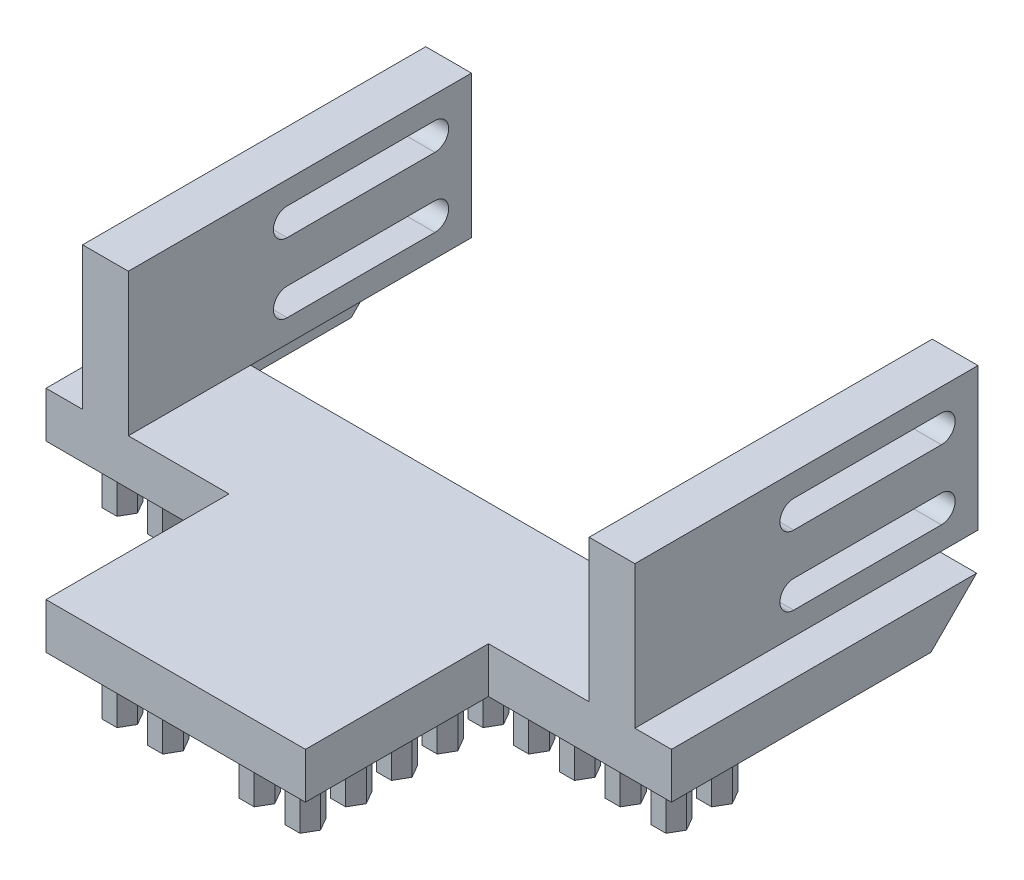
SolidWorks part; units mm, degrees
ref_plane "Front Plane" through (0, 0, 0) normal (0, 0, 1) x (1, 0, 0)
ref_plane "Top Plane" through (0, 0, 0) normal (0, 1, 0) x (1, 0, 0)
ref_plane "Right Plane" through (0, 0, 0) normal (1, 0, 0) x (0, 0, -1)
sketch "Sketch2" plane through (0, 0, 0) normal (0, 1, 0) x (1, 0, 0)
  line L0 (60, 0) -> (-60, 0) construction
  line L1 (-53.2909, -10) -> (-51.6454, -12.85)
  line L2 (-63.2909, 0) -> (-61.6454, -2.85)
  line L3 (-61.6454, -2.85) -> (-58.3546, -2.85)
  line L4 (-58.3546, -2.85) -> (-56.7091, 0)
  line L5 (-56.7091, 0) -> (-58.3546, 2.85)
  line L6 (-58.3546, 2.85) -> (-61.6454, 2.85)
  line L7 (-61.6454, 2.85) -> (-63.2909, 0)
  line L15 (-60, 0) -> (-60, -10) construction
  line L30 (-63.2909, -10) -> (-61.6454, -12.85)
  line L31 (-61.6454, -12.85) -> (-58.3546, -12.85)
  line L32 (-58.3546, -12.85) -> (-56.7091, -10)
  line L33 (-56.7091, -10) -> (-58.3546, -7.15)
  line L34 (-58.3546, -7.15) -> (-61.6454, -7.15)
  line L35 (-61.6454, -7.15) -> (-63.2909, -10)
  line L36 (-51.6454, -12.85) -> (-48.3546, -12.85)
  line L37 (-48.3546, -12.85) -> (-46.7091, -10)
  line L38 (-46.7091, -10) -> (-48.3546, -7.15)
  line L39 (-48.3546, -7.15) -> (-51.6454, -7.15)
  line L40 (-51.6454, -7.15) -> (-53.2909, -10)
  line L41 (-53.2909, 0) -> (-51.6454, -2.85)
  line L42 (-51.6454, -2.85) -> (-48.3546, -2.85)
  line L43 (-48.3546, -2.85) -> (-46.7091, 0)
  line L44 (-46.7091, 0) -> (-48.3546, 2.85)
  line L45 (-48.3546, 2.85) -> (-51.6454, 2.85)
  line L46 (-51.6454, 2.85) -> (-53.2909, 0)
  line L47 (-43.2909, -10) -> (-41.6454, -12.85)
  line L48 (-41.6454, -12.85) -> (-38.3546, -12.85)
  line L49 (-38.3546, -12.85) -> (-36.7091, -10)
  line L50 (-36.7091, -10) -> (-38.3546, -7.15)
  line L51 (-38.3546, -7.15) -> (-41.6454, -7.15)
  line L52 (-41.6454, -7.15) -> (-43.2909, -10)
  line L53 (-43.2909, 0) -> (-41.6454, -2.85)
  line L54 (-41.6454, -2.85) -> (-38.3546, -2.85)
  line L55 (-38.3546, -2.85) -> (-36.7091, 0)
  line L56 (-36.7091, 0) -> (-38.3546, 2.85)
  line L57 (-38.3546, 2.85) -> (-41.6454, 2.85)
  line L58 (-41.6454, 2.85) -> (-43.2909, 0)
  line L59 (-33.2909, -10) -> (-31.6454, -12.85)
  line L60 (-31.6454, -12.85) -> (-28.3546, -12.85)
  line L61 (-28.3546, -12.85) -> (-26.7091, -10)
  line L62 (-26.7091, -10) -> (-28.3546, -7.15)
  line L63 (-28.3546, -7.15) -> (-31.6454, -7.15)
  line L64 (-31.6454, -7.15) -> (-33.2909, -10)
  line L65 (-33.2909, 0) -> (-31.6454, -2.85)
  line L66 (-31.6454, -2.85) -> (-28.3546, -2.85)
  line L67 (-28.3546, -2.85) -> (-26.7091, 0)
  line L68 (-26.7091, 0) -> (-28.3546, 2.85)
  line L69 (-28.3546, 2.85) -> (-31.6454, 2.85)
  line L70 (-31.6454, 2.85) -> (-33.2909, 0)
  line L71 (-23.2909, -10) -> (-21.6454, -12.85)
  line L72 (-21.6454, -12.85) -> (-18.3546, -12.85)
  line L73 (-18.3546, -12.85) -> (-16.7091, -10)
  line L74 (-16.7091, -10) -> (-18.3546, -7.15)
  line L75 (-18.3546, -7.15) -> (-21.6454, -7.15)
  line L76 (-21.6454, -7.15) -> (-23.2909, -10)
  line L77 (-23.2909, 0) -> (-21.6454, -2.85)
  line L78 (-21.6454, -2.85) -> (-18.3546, -2.85)
  line L79 (-18.3546, -2.85) -> (-16.7091, 0)
  line L80 (-16.7091, 0) -> (-18.3546, 2.85)
  line L81 (-18.3546, 2.85) -> (-21.6454, 2.85)
  line L82 (-21.6454, 2.85) -> (-23.2909, 0)
  line L83 (-13.2909, -10) -> (-11.6454, -12.85)
  line L84 (-11.6454, -12.85) -> (-8.3546, -12.85)
  line L85 (-8.3546, -12.85) -> (-6.7091, -10)
  line L86 (-6.7091, -10) -> (-8.3546, -7.15)
  line L87 (-8.3546, -7.15) -> (-11.6454, -7.15)
  line L88 (-11.6454, -7.15) -> (-13.2909, -10)
  line L89 (-13.2909, 0) -> (-11.6454, -2.85)
  line L90 (-11.6454, -2.85) -> (-8.3546, -2.85)
  line L91 (-8.3546, -2.85) -> (-6.7091, 0)
  line L92 (-6.7091, 0) -> (-8.3546, 2.85)
  line L93 (-8.3546, 2.85) -> (-11.6454, 2.85)
  line L94 (-11.6454, 2.85) -> (-13.2909, 0)
  line L95 (-63.2909, -10) -> (-53.2909, -10) construction
  line L96 (-23.2909, -20) -> (-21.6454, -22.85)
  line L97 (-21.6454, -22.85) -> (-18.3546, -22.85)
  line L98 (-18.3546, -22.85) -> (-16.7091, -20)
  line L99 (-16.7091, -20) -> (-18.3546, -17.15)
  line L100 (-18.3546, -17.15) -> (-21.6454, -17.15)
  line L101 (-21.6454, -17.15) -> (-23.2909, -20)
  line L102 (-13.2909, -20) -> (-11.6454, -22.85)
  line L103 (-11.6454, -22.85) -> (-8.3546, -22.85)
  line L104 (-8.3546, -22.85) -> (-6.7091, -20)
  line L105 (-6.7091, -20) -> (-8.3546, -17.15)
  line L106 (-8.3546, -17.15) -> (-11.6454, -17.15)
  line L107 (-11.6454, -17.15) -> (-13.2909, -20)
  line L108 (-23.2909, -30) -> (-21.6454, -32.85)
  line L109 (-21.6454, -32.85) -> (-18.3546, -32.85)
  line L110 (-18.3546, -32.85) -> (-16.7091, -30)
  line L111 (-16.7091, -30) -> (-18.3546, -27.15)
  line L112 (-18.3546, -27.15) -> (-21.6454, -27.15)
  line L113 (-21.6454, -27.15) -> (-23.2909, -30)
  line L114 (-13.2909, -30) -> (-11.6454, -32.85)
  line L115 (-11.6454, -32.85) -> (-8.3546, -32.85)
  line L116 (-8.3546, -32.85) -> (-6.7091, -30)
  line L117 (-6.7091, -30) -> (-8.3546, -27.15)
  line L118 (-8.3546, -27.15) -> (-11.6454, -27.15)
  line L119 (-11.6454, -27.15) -> (-13.2909, -30)
  line L120 (-23.2909, -40) -> (-21.6454, -42.85)
  line L121 (-21.6454, -42.85) -> (-18.3546, -42.85)
  line L122 (-18.3546, -42.85) -> (-16.7091, -40)
  line L123 (-16.7091, -40) -> (-18.3546, -37.15)
  line L124 (-18.3546, -37.15) -> (-21.6454, -37.15)
  line L125 (-21.6454, -37.15) -> (-23.2909, -40)
  line L126 (-13.2909, -40) -> (-11.6454, -42.85)
  line L127 (-11.6454, -42.85) -> (-8.3546, -42.85)
  line L128 (-8.3546, -42.85) -> (-6.7091, -40)
  line L129 (-6.7091, -40) -> (-8.3546, -37.15)
  line L130 (-8.3546, -37.15) -> (-11.6454, -37.15)
  line L131 (-11.6454, -37.15) -> (-13.2909, -40)
  line L132 (-23.2909, -50) -> (-21.6454, -52.85)
  line L133 (-21.6454, -52.85) -> (-18.3546, -52.85)
  line L134 (-18.3546, -52.85) -> (-16.7091, -50)
  line L135 (-16.7091, -50) -> (-18.3546, -47.15)
  line L136 (-18.3546, -47.15) -> (-21.6454, -47.15)
  line L137 (-21.6454, -47.15) -> (-23.2909, -50)
  line L138 (-13.2909, -50) -> (-11.6454, -52.85)
  line L139 (-11.6454, -52.85) -> (-8.3546, -52.85)
  line L140 (-8.3546, -52.85) -> (-6.7091, -50)
  line L141 (-6.7091, -50) -> (-8.3546, -47.15)
  line L142 (-8.3546, -47.15) -> (-11.6454, -47.15)
  line L143 (-11.6454, -47.15) -> (-13.2909, -50)
  line L144 (-23.2909, -10) -> (-23.2909, -20) construction
  line L145 (0, 0) -> (0, -58.3546) construction
  line L146 (23.2909, -10) -> (23.2909, -20) construction
  line L147 (63.2909, -10) -> (53.2909, -10) construction
  line L148 (60, 0) -> (60, -10) construction
  line L149 (11.6454, -47.15) -> (13.2909, -50)
  line L150 (8.3546, -47.15) -> (11.6454, -47.15)
  line L151 (6.7091, -50) -> (8.3546, -47.15)
  line L152 (8.3546, -52.85) -> (6.7091, -50)
  line L153 (11.6454, -52.85) -> (8.3546, -52.85)
  line L154 (13.2909, -50) -> (11.6454, -52.85)
  line L155 (21.6454, -47.15) -> (23.2909, -50)
  line L156 (18.3546, -47.15) -> (21.6454, -47.15)
  line L157 (16.7091, -50) -> (18.3546, -47.15)
  line L158 (18.3546, -52.85) -> (16.7091, -50)
  line L159 (21.6454, -52.85) -> (18.3546, -52.85)
  line L160 (23.2909, -50) -> (21.6454, -52.85)
  line L161 (11.6454, -37.15) -> (13.2909, -40)
  line L162 (8.3546, -37.15) -> (11.6454, -37.15)
  line L163 (6.7091, -40) -> (8.3546, -37.15)
  line L164 (8.3546, -42.85) -> (6.7091, -40)
  line L165 (11.6454, -42.85) -> (8.3546, -42.85)
  line L166 (13.2909, -40) -> (11.6454, -42.85)
  line L167 (21.6454, -37.15) -> (23.2909, -40)
  line L168 (18.3546, -37.15) -> (21.6454, -37.15)
  line L169 (16.7091, -40) -> (18.3546, -37.15)
  line L170 (18.3546, -42.85) -> (16.7091, -40)
  line L171 (21.6454, -42.85) -> (18.3546, -42.85)
  line L172 (23.2909, -40) -> (21.6454, -42.85)
  line L173 (11.6454, -27.15) -> (13.2909, -30)
  line L174 (8.3546, -27.15) -> (11.6454, -27.15)
  line L175 (6.7091, -30) -> (8.3546, -27.15)
  line L176 (8.3546, -32.85) -> (6.7091, -30)
  line L177 (11.6454, -32.85) -> (8.3546, -32.85)
  line L178 (13.2909, -30) -> (11.6454, -32.85)
  line L179 (21.6454, -27.15) -> (23.2909, -30)
  line L180 (18.3546, -27.15) -> (21.6454, -27.15)
  line L181 (16.7091, -30) -> (18.3546, -27.15)
  line L182 (18.3546, -32.85) -> (16.7091, -30)
  line L183 (21.6454, -32.85) -> (18.3546, -32.85)
  line L184 (23.2909, -30) -> (21.6454, -32.85)
  line L185 (11.6454, -17.15) -> (13.2909, -20)
  line L186 (8.3546, -17.15) -> (11.6454, -17.15)
  line L187 (6.7091, -20) -> (8.3546, -17.15)
  line L188 (8.3546, -22.85) -> (6.7091, -20)
  line L189 (11.6454, -22.85) -> (8.3546, -22.85)
  line L190 (13.2909, -20) -> (11.6454, -22.85)
  line L191 (21.6454, -17.15) -> (23.2909, -20)
  line L192 (18.3546, -17.15) -> (21.6454, -17.15)
  line L193 (16.7091, -20) -> (18.3546, -17.15)
  line L194 (18.3546, -22.85) -> (16.7091, -20)
  line L195 (21.6454, -22.85) -> (18.3546, -22.85)
  line L196 (23.2909, -20) -> (21.6454, -22.85)
  line L197 (11.6454, 2.85) -> (13.2909, 0)
  line L198 (8.3546, 2.85) -> (11.6454, 2.85)
  line L199 (6.7091, 0) -> (8.3546, 2.85)
  line L200 (8.3546, -2.85) -> (6.7091, 0)
  line L201 (11.6454, -2.85) -> (8.3546, -2.85)
  line L202 (13.2909, 0) -> (11.6454, -2.85)
  line L203 (11.6454, -7.15) -> (13.2909, -10)
  line L204 (8.3546, -7.15) -> (11.6454, -7.15)
  line L205 (6.7091, -10) -> (8.3546, -7.15)
  line L206 (8.3546, -12.85) -> (6.7091, -10)
  line L207 (11.6454, -12.85) -> (8.3546, -12.85)
  line L208 (13.2909, -10) -> (11.6454, -12.85)
  line L209 (21.6454, 2.85) -> (23.2909, 0)
  line L210 (18.3546, 2.85) -> (21.6454, 2.85)
  line L211 (16.7091, 0) -> (18.3546, 2.85)
  line L212 (18.3546, -2.85) -> (16.7091, 0)
  line L213 (21.6454, -2.85) -> (18.3546, -2.85)
  line L214 (23.2909, 0) -> (21.6454, -2.85)
  line L215 (21.6454, -7.15) -> (23.2909, -10)
  line L216 (18.3546, -7.15) -> (21.6454, -7.15)
  line L217 (16.7091, -10) -> (18.3546, -7.15)
  line L218 (18.3546, -12.85) -> (16.7091, -10)
  line L219 (21.6454, -12.85) -> (18.3546, -12.85)
  line L220 (23.2909, -10) -> (21.6454, -12.85)
  line L221 (31.6454, 2.85) -> (33.2909, 0)
  line L222 (28.3546, 2.85) -> (31.6454, 2.85)
  line L223 (26.7091, 0) -> (28.3546, 2.85)
  line L224 (28.3546, -2.85) -> (26.7091, 0)
  line L225 (31.6454, -2.85) -> (28.3546, -2.85)
  line L226 (33.2909, 0) -> (31.6454, -2.85)
  line L227 (31.6454, -7.15) -> (33.2909, -10)
  line L228 (28.3546, -7.15) -> (31.6454, -7.15)
  line L229 (26.7091, -10) -> (28.3546, -7.15)
  line L230 (28.3546, -12.85) -> (26.7091, -10)
  line L231 (31.6454, -12.85) -> (28.3546, -12.85)
  line L232 (33.2909, -10) -> (31.6454, -12.85)
  line L233 (41.6454, 2.85) -> (43.2909, 0)
  line L234 (38.3546, 2.85) -> (41.6454, 2.85)
  line L235 (36.7091, 0) -> (38.3546, 2.85)
  line L236 (38.3546, -2.85) -> (36.7091, 0)
  line L237 (41.6454, -2.85) -> (38.3546, -2.85)
  line L238 (43.2909, 0) -> (41.6454, -2.85)
  line L239 (41.6454, -7.15) -> (43.2909, -10)
  line L240 (38.3546, -7.15) -> (41.6454, -7.15)
  line L241 (36.7091, -10) -> (38.3546, -7.15)
  line L242 (38.3546, -12.85) -> (36.7091, -10)
  line L243 (41.6454, -12.85) -> (38.3546, -12.85)
  line L244 (43.2909, -10) -> (41.6454, -12.85)
  line L245 (51.6454, 2.85) -> (53.2909, 0)
  line L246 (48.3546, 2.85) -> (51.6454, 2.85)
  line L247 (46.7091, 0) -> (48.3546, 2.85)
  line L248 (48.3546, -2.85) -> (46.7091, 0)
  line L249 (51.6454, -2.85) -> (48.3546, -2.85)
  line L250 (53.2909, 0) -> (51.6454, -2.85)
  line L251 (51.6454, -7.15) -> (53.2909, -10)
  line L252 (48.3546, -7.15) -> (51.6454, -7.15)
  line L253 (46.7091, -10) -> (48.3546, -7.15)
  line L254 (48.3546, -12.85) -> (46.7091, -10)
  line L255 (51.6454, -12.85) -> (48.3546, -12.85)
  line L256 (61.6454, -7.15) -> (63.2909, -10)
  line L257 (58.3546, -7.15) -> (61.6454, -7.15)
  line L258 (56.7091, -10) -> (58.3546, -7.15)
  line L259 (58.3546, -12.85) -> (56.7091, -10)
  line L260 (61.6454, -12.85) -> (58.3546, -12.85)
  line L261 (63.2909, -10) -> (61.6454, -12.85)
  line L262 (61.6454, 2.85) -> (63.2909, 0)
  line L263 (58.3546, 2.85) -> (61.6454, 2.85)
  line L264 (56.7091, 0) -> (58.3546, 2.85)
  line L265 (58.3546, -2.85) -> (56.7091, 0)
  line L266 (61.6454, -2.85) -> (58.3546, -2.85)
  line L267 (63.2909, 0) -> (61.6454, -2.85)
  line L268 (53.2909, -10) -> (51.6454, -12.85)
  line L269 (-68.3546, -18.3546) -> (-68.3546, 48.3546) construction
  line L270 (-68.3546, 48.3546) -> (-58.3546, 48.3546) construction
  line L271 (-58.3546, 48.3546) -> (-58.3546, 8.3546) construction
  line L272 (-58.3546, 8.3546) -> (58.3546, 8.3546) construction
  line L273 (58.3546, 8.3546) -> (58.3546, 48.3546) construction
  line L274 (58.3546, 48.3546) -> (68.3546, 48.3546) construction
  line L275 (68.3546, 48.3546) -> (68.3546, -18.3546) construction
  line L276 (68.3546, -18.3546) -> (28.3546, -18.3546) construction
  line L277 (28.3546, -18.3546) -> (28.3546, -58.3546) construction
  line L278 (28.3546, -58.3546) -> (-28.3546, -58.3546) construction
  line L279 (-28.3546, -58.3546) -> (-28.3546, -18.3546) construction
  line L280 (-28.3546, -18.3546) -> (-68.3546, -18.3546) construction
  line L281 (-60, -12.85) -> (-60, -18.3546) construction
  line L282 (-20, -52.85) -> (-20, -58.3546) construction
  line L283 (-40, 2.85) -> (-40, 8.3546) construction
  line L284 (-62.85, -10) -> (-68.3546, -10) construction
  line L285 (-22.85, -50) -> (-28.3546, -50) construction
  circle A0 centre (-60, 0) radius 2.85 construction
  circle A1 centre (60, -10) radius 2.85 construction
  circle A2 centre (60, 0) radius 2.85 construction
  circle A3 centre (-20, -50) radius 2.85 construction
  circle A4 centre (-60, -10) radius 2.85 construction
  point P3 (-10, 0)
  point P257 (10, 0)
  dimension "D2" = 5.7
  dimension "D9" = 40
  dimension "D1" = 60
  dimension "D3" = 10
  dimension "D4" = 10
  dimension "D5" = 6
  dimension "D6" = 10
  dimension "D8" = 10
  dimension "D7" = 5
sketch "Sketch3" plane through (0, 0, 0) normal (0, 1, 0) x (1, 0, 0)
  line L0 (68.3546, 48.3546) -> (68.3546, -18.3546) construction
  line L1 (58.3546, 48.3546) -> (68.3546, 48.3546) construction
  line L2 (58.3546, 8.3546) -> (58.3546, 48.3546) construction
  line L3 (68.3546, -18.3546) -> (28.3546, -18.3546) construction
  line L4 (28.3546, -18.3546) -> (28.3546, -58.3546) construction
  line L5 (28.3546, -58.3546) -> (-28.3546, -58.3546) construction
  line L6 (-28.3546, -58.3546) -> (-28.3546, -18.3546) construction
  line L7 (-28.3546, -18.3546) -> (-68.3546, -18.3546) construction
  line L8 (-58.3546, 8.3546) -> (58.3546, 8.3546) construction
  line L9 (-68.3546, 48.3546) -> (-58.3546, 48.3546) construction
  line L10 (-58.3546, 48.3546) -> (-58.3546, 8.3546) construction
  line L11 (-68.3546, -18.3546) -> (-68.3546, 48.3546) construction
  line L12 (68.3546, 48.3546) -> (68.3546, -18.3546)
  line L13 (58.3546, 48.3546) -> (68.3546, 48.3546)
  line L14 (58.3546, 8.3546) -> (58.3546, 48.3546)
  line L15 (68.3546, -18.3546) -> (28.3546, -18.3546)
  line L16 (28.3546, -18.3546) -> (28.3546, -58.3546)
  line L17 (28.3546, -58.3546) -> (-28.3546, -58.3546)
  line L18 (-28.3546, -58.3546) -> (-28.3546, -18.3546)
  line L19 (-28.3546, -18.3546) -> (-68.3546, -18.3546)
  line L20 (-58.3546, 8.3546) -> (58.3546, 8.3546)
  line L21 (-68.3546, 48.3546) -> (-58.3546, 48.3546)
  line L22 (-58.3546, 48.3546) -> (-58.3546, 8.3546)
  line L23 (-68.3546, -18.3546) -> (-68.3546, 48.3546)
extrude "Boss-Extrude1" add sketch "Sketch3" along normal blind 10
extrude "Boss-Extrude2" add sketch "Sketch2" against normal blind 12
ref_plane "Plane1" through (-58.3546, 0, 0) normal (-1, 0, 0) x (0, 0, 1)
sketch "Sketch4" plane through (-58.3546, 0, 0) normal (-1, 0, 0) x (0, 0, 1)
  line L0 (18.3546, 10) -> (18.3546, 0) construction
  line L1 (-56.6454, 10) -> (18.3546, 10)
  line L2 (-56.6454, 10) -> (-56.6454, 41.1554)
  line L3 (-56.6454, 41.1554) -> (18.3546, 41.1554)
  line L4 (18.3546, 10) -> (18.3546, 41.1554)
  line L5 (-48.6454, 18) -> (-16.3546, 18) construction
  line L6 (-48.6454, 21) -> (-16.3546, 21)
  line L7 (-48.6454, 15) -> (-16.3546, 15)
  line L8 (-48.6454, 33.1554) -> (-16.3546, 33.1554) construction
  line L9 (-48.6454, 36.1554) -> (-16.3546, 36.1554)
  line L10 (-48.6454, 30.1554) -> (-16.3546, 30.1554)
  line L11 (-48.6454, 30.1554) -> (-48.6454, 36.1554) construction
  line L12 (-48.6454, 15) -> (-48.6454, 21) construction
  line L13 (-51.6454, 41.1554) -> (-51.6454, 10) construction
  line L14 (-56.6454, 10) -> (-51.6454, 15) construction
  line L15 (-56.6454, 15) -> (18.3546, 15) construction
  line L17 (-13.3546, 41.1554) -> (-13.3546, 10) construction
  line L18 (-56.6454, 41.1554) -> (-51.6454, 36.1554) construction
  line L19 (-56.6454, 36.1554) -> (18.3546, 36.1554) construction
  line L20 (-16.3546, 18) -> (-25.1046, 33.1554) construction
  line L21 (-8.3546, 10) -> (-48.3546, 10) construction
  arc A0 (-48.6454, 21) -> (-48.6454, 15) centre (-48.6454, 18) ccw
  arc A1 (-16.3546, 15) -> (-16.3546, 21) centre (-16.3546, 18) ccw
  arc A2 (-48.6454, 36.1554) -> (-48.6454, 30.1554) centre (-48.6454, 33.1554) ccw
  arc A3 (-16.3546, 30.1554) -> (-16.3546, 36.1554) centre (-16.3546, 33.1554) ccw
  point P7 (-32.5, 18)
  point P14 (-32.5, 33.1554)
  point P37 (-30.8546, 18)
  point P40 (-13.3546, 18)
  point P41 (-13.3546, 10)
  point P42 (-8.3546, 10)
  dimension "D1" = 45
  dimension "D2" = 45
  dimension "D3" = 75
  dimension "D4" = 60
  dimension "D5" = 6
  dimension "D6" = 17.5
  dimension "D7" = 5
  dimension "D8" = 5
  dimension "D9" = 17.5
extrude "Boss-Extrude3" add sketch "Sketch4" against normal blind 8 and the other way blind 2
mirror "Mirror1" about plane through (0, 0, 0) normal (1, 0, 0) of "Boss-Extrude3"
chamfer "Chamfer1" distance 10 angle 45 2 edges at (63.3546, 0, -48.3546) (-63.3546, 0, -48.3546)
